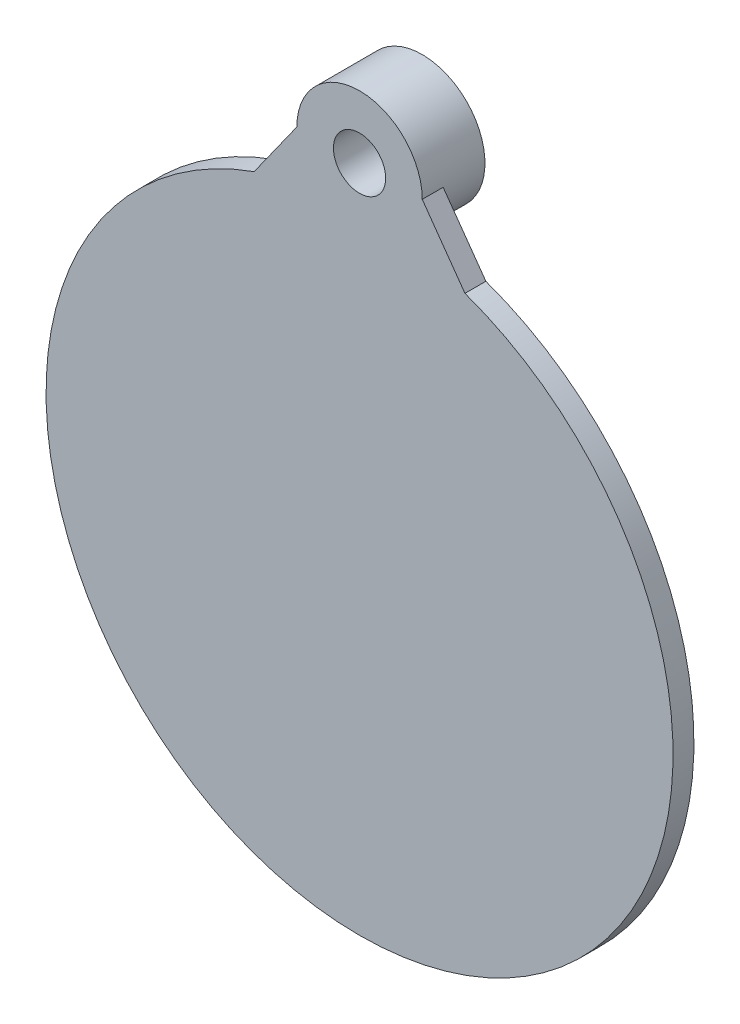
SolidWorks part; units mm, degrees
ref_plane "Front Plane" through (0, 0, 0) normal (0, 0, 1) x (1, 0, 0)
ref_plane "Top Plane" through (0, 0, 0) normal (0, 1, 0) x (1, 0, 0)
ref_plane "Right Plane" through (0, 0, 0) normal (1, 0, 0) x (0, 0, -1)
sketch "Sketch1" plane through (0, 0, 0) normal (0, 0, 1) x (1, 0, 0)
  line L0 (-9.525, 53.975) -> (-16.0135, 44.8521)
  line L1 (9.525, 53.975) -> (16.0135, 44.8521)
  circle A0 centre (0, 0) radius 37.9
  arc A1 (-16.0135, 44.8521) -> (16.0135, 44.8521) centre (0, 0) ccw
  circle A2 centre (0, 53.975) radius 3.9688
  arc A3 (9.525, 53.975) -> (-9.525, 53.975) centre (0, 53.975) ccw
  dimension "D1" = 75.8
  dimension "D2" = 95.25
  dimension "D3" = 53.975
extrude "Boss-Extrude1" add sketch "Sketch1" along normal blind 3.175
sketch "Sketch2" plane through (0, 0, 3.175) normal (0, 0, 1) x (1, 0, 0)
  circle A0 centre (0, 0) radius 37.9
extrude "Boss-Extrude3" add sketch "Sketch2" against normal blind 6.35
fillet "Fillet1" radius 0.4 1 edges at (37.9, 0, -3.175)
sketch "Sketch4" plane through (0, 0, 0) normal (0, 0, -1) x (-1, 0, 0)
  circle A0 centre (0, 53.975) radius 3.9688
  circle A1 centre (0, 53.975) radius 9.525
extrude "Boss-Extrude4" add sketch "Sketch4" along normal blind 6.35
chamfer "Chamfer1" distance 0.2 angle 45 1 edges at (-3.9688, 53.975, -6.35)
